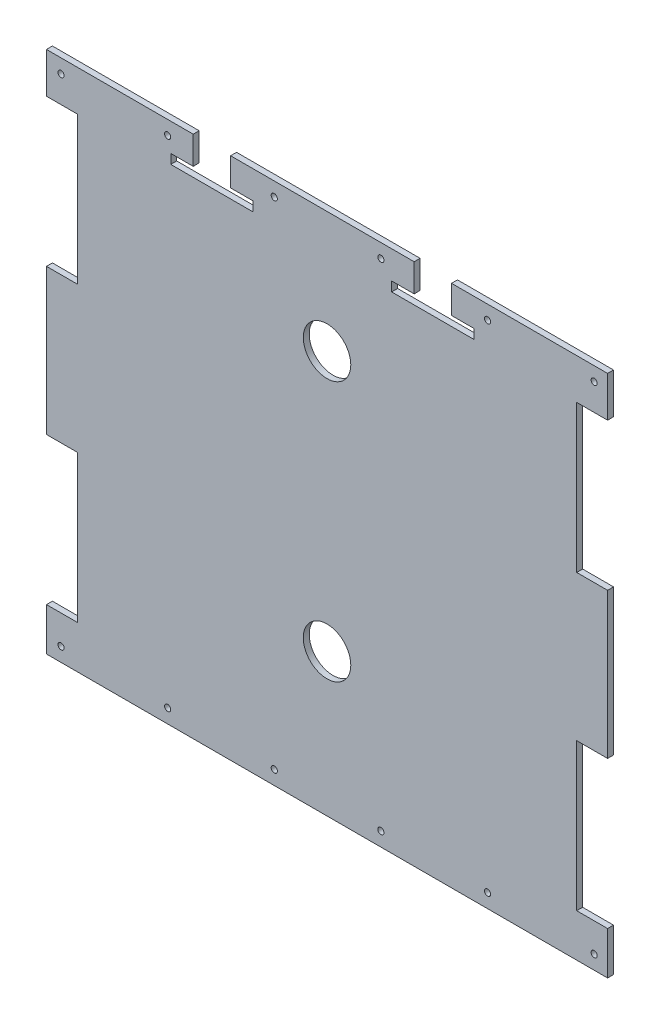
SolidWorks part; units mm, degrees
material "PBT General Purpose"
ref_plane "Front" through (0, 0, 0) normal (0, 0, 1) x (1, 0, 0)
ref_plane "Top" through (0, 0, 0) normal (0, 1, 0) x (1, 0, 0)
ref_plane "Right" through (0, 0, 0) normal (1, 0, 0) x (0, 0, -1)
sketch "Sketch5" plane through (0, 0, 0) normal (0, 0, 1) x (1, 0, 0)
  line L0 (47.1246, -7.4523) -> (30.6146, -7.4523)
  line L1 (-252.8494, 249.5587) -> (-174.4024, 249.5587)
  line L2 (-252.8494, 249.5587) -> (-252.8494, 227.8859)
  line L3 (-252.8494, -30.3493) -> (47.1246, -30.3493)
  line L4 (47.1246, 249.5587) -> (47.1246, 227.8859)
  line L5 (30.6146, -7.4523) -> (30.6146, 71.2877)
  line L6 (30.6146, 71.2877) -> (47.1246, 71.2877)
  line L8 (47.1246, -7.4523) -> (47.1246, -30.3493)
  line L9 (47.1246, 149.1459) -> (30.6146, 149.1459)
  line L10 (30.6146, 149.1459) -> (30.6146, 227.8859)
  line L11 (30.6146, 227.8859) -> (47.1246, 227.8859)
  line L13 (47.1246, 149.1459) -> (47.1246, 71.2877)
  line L14 (-252.8494, 227.8859) -> (-236.3394, 227.8859)
  line L15 (-236.3394, 227.8859) -> (-236.3394, 149.1459)
  line L16 (-236.3394, 149.1459) -> (-252.8494, 149.1459)
  line L18 (-252.8494, 149.1459) -> (-252.8494, 71.2877)
  line L19 (-252.8494, 71.2877) -> (-236.3394, 71.2877)
  line L20 (-236.3394, 71.2877) -> (-236.3394, -7.4523)
  line L21 (-236.3394, -7.4523) -> (-252.8494, -7.4523)
  line L23 (-252.8494, -7.4523) -> (-252.8494, -30.3493)
  line L24 (47.1246, -22.8907) -> (-72.4065, -22.8907) construction
  line L25 (-252.8494, 242.1016) -> (-174.4024, 242.1016) construction
  line L26 (-75.7065, -22.8907) -> (-252.8494, -22.8907) construction
  line L27 (-56.3024, 249.5587) -> (-56.3024, 234.6507)
  line L28 (-56.3024, 229.5587) -> (-36.3024, 229.5587)
  line L29 (-36.3024, 234.6507) -> (-36.3024, 249.5587)
  line L31 (-174.4024, 249.5587) -> (-174.4024, 234.6507)
  line L32 (-174.4024, 229.5587) -> (-154.4024, 229.5587)
  line L33 (-154.4024, 234.6507) -> (-154.4024, 249.5587)
  line L35 (-154.4024, 249.5587) -> (-56.3024, 249.5587)
  line L36 (-154.4024, 242.1016) -> (-56.3024, 242.1016) construction
  line L37 (-36.3024, 249.5587) -> (47.1246, 249.5587)
  line L38 (-36.3024, 242.1016) -> (47.1246, 242.1016) construction
  line L39 (-36.3024, 234.6507) -> (-24.3024, 234.6507)
  line L40 (-252.8494, 234.6507) -> (47.1506, 234.6507) construction
  line L41 (-24.3024, 234.6507) -> (-24.3024, 229.5587)
  line L42 (-24.3024, 229.5587) -> (-36.3024, 229.5587)
  line L43 (-56.3024, 234.6507) -> (-68.3024, 234.6507)
  line L44 (-174.4024, 234.6507) -> (-186.4024, 234.6507)
  line L45 (-54.6336, 234.6507) -> (-154.6336, 234.6507) construction
  line L46 (-68.3024, 234.6507) -> (-68.3024, 229.5587)
  line L47 (-68.3024, 229.5587) -> (-56.3024, 229.5587)
  line L48 (-186.4024, 234.6507) -> (-186.4024, 229.5587)
  line L49 (-186.4024, 229.5587) -> (-174.4024, 229.5587)
  line L50 (-154.4024, 234.6507) -> (-142.4024, 234.6507)
  line L51 (-142.4024, 234.6507) -> (-142.4024, 229.5587)
  line L52 (-142.4024, 229.5587) -> (-154.4024, 229.5587)
  circle A8 centre (39.9435, -22.8907) radius 1.65
  circle A10 centre (-17.0565, -22.8907) radius 1.65
  circle A11 centre (-74.0565, -22.8907) radius 1.65
  circle A12 centre (-131.0565, -22.8907) radius 1.65
  circle A13 centre (-188.0565, -22.8907) radius 1.65
  circle A14 centre (-245.0565, -22.8907) radius 1.65
  circle A15 centre (39.9435, 242.1016) radius 1.65
  circle A16 centre (-17.0565, 242.1016) radius 1.65
  circle A17 centre (-74.0565, 242.1016) radius 1.65
  circle A18 centre (-131.0565, 242.1016) radius 1.65
  circle A19 centre (-188.0565, 242.1016) radius 1.65
  circle A20 centre (-245.0565, 242.1016) radius 1.65
  circle A22 centre (-102.8624, 184.8543) radius 12.7
  circle A23 centre (-102.8624, 45.8507) radius 12.7
  point P12 (38.8696, 149.1459)
  dimension "D10" = 3.3
  dimension "D12" = 3.3
  dimension "D14" = 25.4
  dimension "D15" = 25.4
  dimension "D1" = 299.974
  dimension "D2" = 279.908
  dimension "D3" = 16.51
  dimension "D4" = 16.51
  dimension "D5" = 16.51
  dimension "D6" = 78.74
  dimension "D7" = 78.74
  dimension "D8" = 78.74
  dimension "D9" = 16.51
  dimension "D16" = 76.2
  dimension "D17" = 20
  dimension "D18" = 20
  dimension "D19" = 12
  dimension "D20" = 12
  dimension "D21" = 12
  dimension "D22" = 12
  dimension "D11" = 6
  dimension "D13" = 6
extrude "Boss-Extrude1" add sketch "Sketch5" along normal blind 3.175
